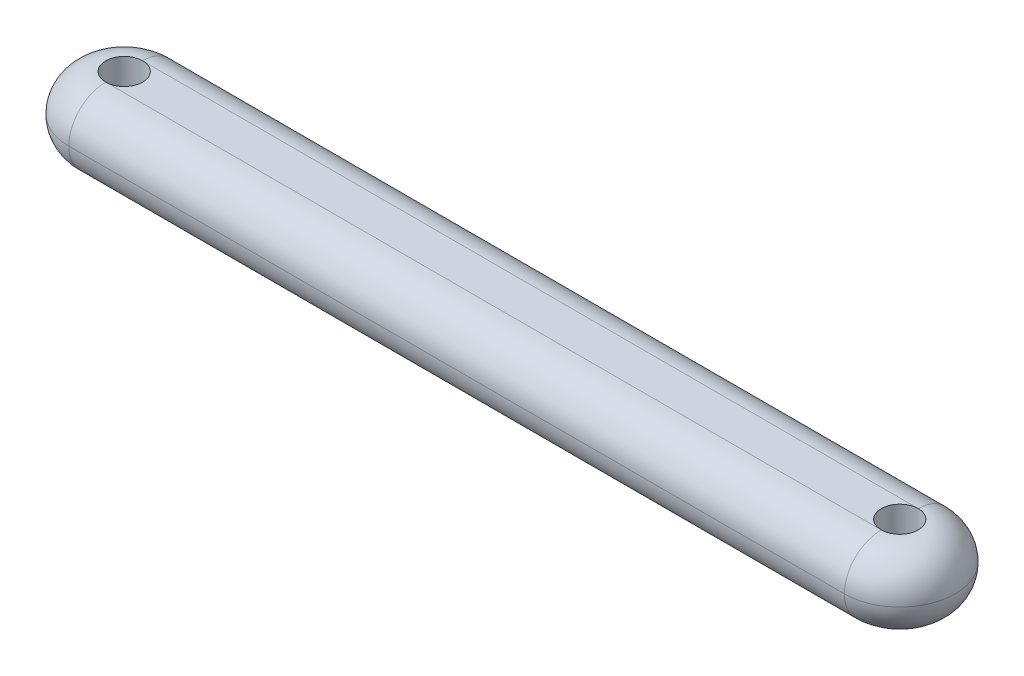
SolidWorks part; units mm, degrees
ref_plane "Alzado" through (0, 0, 0) normal (1, 0, 0) x (0, 1, 0)
ref_plane "Planta" through (0, 0, 0) normal (0, 0, 1) x (0, 1, 0)
ref_plane "Vista lateral" through (0, 0, 0) normal (0, 1, 0) x (-1, 0, 0)
sketch "Croquis1" plane through (0, 0, 0) normal (0, 1, 0) x (-1, 0, 0)
  line L0 (0, 0) -> (105, 0) construction
  line L1 (0, 0) -> (105, 0) construction
  line L2 (0, 7.5) -> (105, 7.5)
  line L3 (0, -7.5) -> (105, -7.5)
  arc A0 (0, 7.5) -> (0, -7.5) centre (0, 0) ccw
  arc A1 (105, -7.5) -> (105, 7.5) centre (105, 0) ccw
  circle A2 centre (0, 0) radius 2.5
  circle A3 centre (105, 0) radius 2.5
  point P3 (52.5, 0)
  dimension "D3" = 5
  dimension "D1" = 105
  dimension "D2" = 15
extrude "Saliente-Extruir1" add sketch "Croquis1" along normal mid plane 10
fillet "Redondeo1" radius 5 8 edges at (7.5, 5, 0) (-52.5, 5, 7.5) (-112.5, 5, 0) (7.5, -5, 0) (-52.5, -5, 7.5) (-112.5, -5, 0) (-52.5, 5, -7.5) (-52.5, -5, -7.5)
equation "\"ancho\"= 15"
equation "\"esp\"= 10"
equation "\"Lbarra05\"=105"
equation "\"agujeros\"= 5"
equation "\"D1@Croquis1\"=\"Lbarra05\""
equation "\"D2@Croquis1\"=\"ancho\""
equation "\"D3@Croquis1\"=\"agujeros\""
equation "\"D1@Saliente-Extruir1\"=\"esp\""
equation "\"D1@Redondeo1\"=\"esp\"/2"
